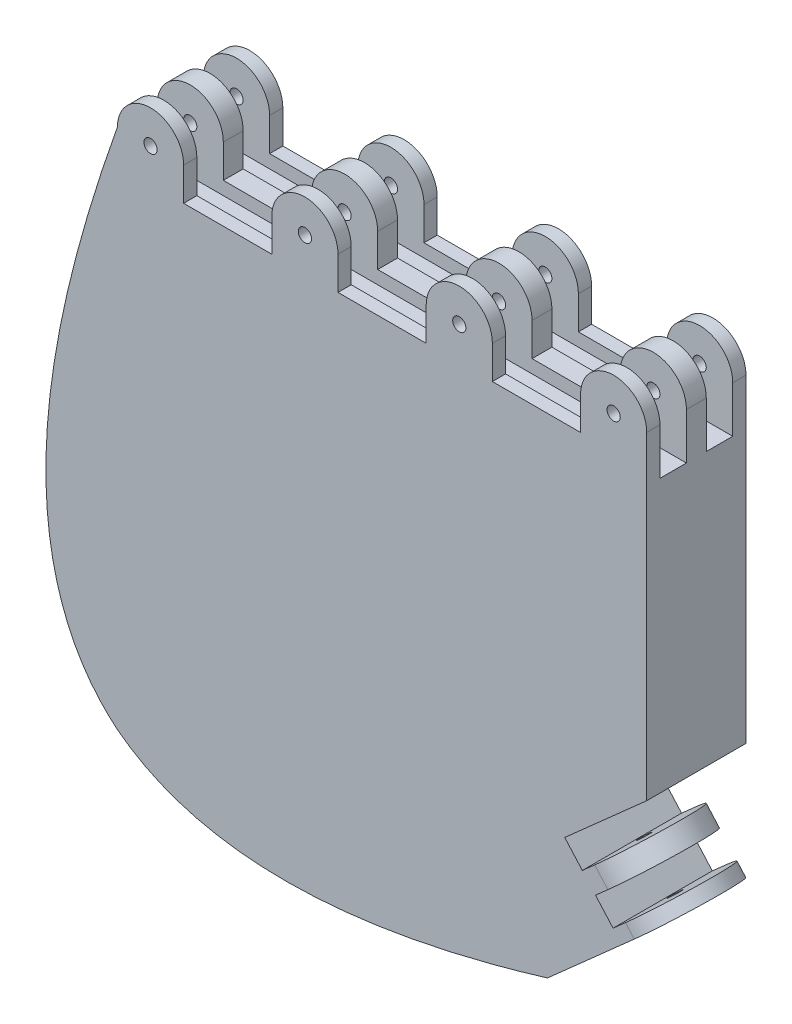
SolidWorks part; units mm, degrees
ref_plane "Plan de face" through (0, 0, 0) normal (0, 0, 1) x (1, 0, 0)
ref_plane "Plan de dessus" through (0, 0, 0) normal (0, 1, 0) x (1, 0, 0)
ref_plane "Plan de droite" through (0, 0, 0) normal (1, 0, 0) x (0, 0, -1)
sketch "Esquisse1" plane through (0, 0, 0) normal (0, 0, 1) x (1, 0, 0)
  line L2 (-10, -18.9105) -> (8.7187, -2.288)
  line L3 (8.7187, -2.288) -> (7.3907, -0.7925)
  line L4 (7.3907, -0.7925) -> (-0.0867, -7.4325)
  line L5 (-0.0867, -7.4325) -> (-2.7427, -4.4416)
  line L6 (-70, 60) -> (-70, 0) construction
  line L7 (-2.7427, -4.4416) -> (4.7347, 2.1984)
  line L8 (4.7347, 2.1984) -> (2.7427, 4.4416)
  line L9 (2.7427, 4.4416) -> (-4.7347, -2.1984)
  line L10 (-4.7347, -2.1984) -> (-7.3907, 0.7925)
  line L11 (-7.3907, 0.7925) -> (5, 11.7957)
  line L12 (5, 11.7957) -> (5, 65)
  line L13 (5, 65) -> (-5, 65)
  line L14 (-5, 65) -> (-5, 55)
  line L15 (-5, 55) -> (-18.3333, 55)
  line L16 (-18.3333, 55) -> (-18.3333, 65)
  line L17 (-18.3333, 65) -> (-28.3333, 65)
  line L18 (-28.3333, 65) -> (-28.3333, 55)
  line L19 (-28.3333, 55) -> (-41.6667, 55)
  line L20 (-41.6667, 55) -> (-41.6667, 65)
  line L21 (-41.6667, 65) -> (-51.6667, 65)
  line L22 (-51.6667, 65) -> (-51.6667, 55)
  line L23 (-51.6667, 55) -> (-65, 55)
  line L24 (-65, 55) -> (-65, 65)
  line L25 (-65, 65) -> (-75, 65)
  line L26 (-75, 65) -> (-75, -18.9105) construction
  line L27 (-75, -18.9105) -> (-10, -18.9105) construction
  line L28 (-70, 60) -> (-46.6667, 60) construction
  line L29 (0, 0) -> (37.3866, 33.2) construction
  line L30 (0, 60) -> (0, 0) construction
  line L31 (-23.3333, 60) -> (0, 60) construction
  line L32 (-46.6667, 60) -> (-23.3333, 60) construction
  line L33 (-65, 60) -> (-75, 60)
  line L34 (-41.6667, 60) -> (-51.6667, 60)
  line L35 (-18.3333, 60) -> (-28.3333, 60)
  line L36 (-5, 60) -> (5, 60)
  circle A0 centre (0, 60) radius 1
  circle A1 centre (-23.3333, 60) radius 1
  circle A2 centre (-70, 60) radius 1
  circle A3 centre (-46.6667, 60) radius 1
  arc A4 (-5, 60) -> (5, 60) centre (0, 60) cw
  arc A5 (-28.3333, 60) -> (-18.3333, 60) centre (-23.3333, 60) cw
  arc A6 (-51.6667, 60) -> (-41.6667, 60) centre (-46.6667, 60) cw
  arc A7 (-75, 60) -> (-65, 60) centre (-70, 60) cw
  spline S0 degree 2 poles (-75, 65) (-116.9553, -51.4105) (-10, -18.9105) knots 0 0 0 1 1 1
  spline S1 degree 2 poles (-75, 60) (-114.4553, -51.4105) (-10, -18.9105) knots 0 0 0 1 1 1
  point P31 (3.7387, 3.32)
  dimension "D26" = 2
  dimension "D27" = 2
  dimension "D30" = 2
  dimension "D31" = 2
  dimension "D1" = 5
  dimension "D2" = 4
  dimension "D3" = 0
  dimension "D4" = 2
  dimension "D5" = 3
  dimension "D6" = 4
  dimension "D7" = 5
  dimension "D8" = 5
  dimension "D9" = 5
  dimension "D10" = 10
  dimension "D11" = 5
  dimension "D12" = 5
  dimension "D13" = 5
  dimension "D14" = 5
  dimension "D15" = 5
  dimension "D16" = 5
  dimension "D17" = 5
  dimension "D18" = 5
  dimension "D19" = 5
  dimension "D20" = 5
  dimension "D21" = 5
  dimension "D22" = 5
  dimension "D23" = 5
  dimension "D24" = 5
  dimension "D25" = 65
  dimension "D28" = 10
  dimension "D29" = 10
extrude "Boss.-Extru.1" add sketch "Esquisse1" along normal blind 12.5 and the other way blind 2.5 contours L33 S1 S0 L2 L3 L4 L5 L7 L8 L9 L10 L11 L12 L36 A0 L14 L15 L16 L35 A1 L18 L19 L20 L34 A3 L22 L23 L24 A2 | A7 L33 A2 | A6 L34 A3 | A5 L35 A1 | A4 L36 A0 region at (-40.161, 17.9034, 0) region at (-70, 62.1928, 0) region at (-46.6667, 62.1928, 0) region at (0, 62.1928, 0) region at (-23.3333, 62.1928, 0)
sketch "Esquisse2" plane through (5, 0, 0) normal (1, 0, 0) x (0, 0, -1)
  line L0 (-12.5, 60) -> (2.5, 60)
  line L1 (2.5, 60) -> (2.5, 53)
  line L2 (2.5, 11.7957) -> (2.5, 60) construction
  line L3 (2.5, 53) -> (-12.5, 53)
  line L4 (-12.5, 11.7957) -> (-12.5, 60) construction
  line L5 (-12.5, 53) -> (-12.5, 65)
  line L6 (-12.5, 65) -> (2.5, 65)
  line L7 (2.5, 65) -> (2.5, 53)
  line L9 (-10.5, 65) -> (-6.5, 65)
  line L11 (-6.5, 65) -> (-3.5, 65)
  line L13 (-3.5, 65) -> (0.5, 65)
  line L15 (-10.5, 65) -> (-10.5, 53)
  line L16 (-10.5, 53) -> (-6.5, 53)
  line L17 (-6.5, 53) -> (-6.5, 65)
  line L18 (-3.5, 65) -> (-3.5, 53)
  line L19 (-3.5, 53) -> (0.5, 53)
  line L20 (0.5, 53) -> (0.5, 65)
  line L21 (-10.5, 53) -> (-6.5, 53)
  line L22 (-3.5, 53) -> (0.5, 53)
  line L23 (-10.5, 65) -> (-10.5, 53)
  line L24 (-10.5, 65) -> (-6.5, 65)
  line L25 (-10.5, 53) -> (-6.5, 53)
  line L26 (-6.5, 65) -> (-6.5, 53)
  line L27 (-3.5, 65) -> (-3.5, 53)
  line L28 (-3.5, 65) -> (0.5, 65)
  line L29 (-3.5, 53) -> (0.5, 53)
  line L30 (0.5, 65) -> (0.5, 53)
  dimension "D1" = 12
  dimension "D2" = 7
  dimension "D3" = 3
  dimension "D4" = 4
  dimension "D5" = 2
  dimension "D6" = 4
  dimension "D7" = 12
  dimension "D8" = 12
extrude "Enlèv. mat.-Extru.1" cut sketch "Esquisse2" against normal through all contours L0 L6 | L9 L0 | L0 L6 | L13 L0 | L23 L24 L26 L25 | L27 L28 L30 L29 region at (5, 62.5, 8.5) region at (5, 56.5, 8.5) region at (5, 62.5, 1.5) region at (5, 56.5, 1.5)
sketch "Esquisse3" plane through (4.98, -5.608, 0) normal (0.664, -0.7477, 0) x (0.7477, 0.664, 0)
  line L0 (-2.5, 12.5) -> (-2.5, -2.5)
  line L1 (-20.0339, 12.5) -> (5, 12.5) construction
  line L2 (-20.0339, -2.5) -> (5, -2.5) construction
  line L3 (5, -2.5) -> (5, 12.5) construction
  line L4 (-2.5, 12.5) -> (5, 12.5)
  line L5 (5, 12.5) -> (5, -2.5)
  line L6 (5, -2.5) -> (-2.5, -2.5)
  arc A0 (-2.5, 12.5) -> (-2.5, -2.5) centre (-2.5, 5) cw
  circle A1 centre (-2.5, 5) radius 1
  line M3 (5, -2.5) -> (5, 12.5)
  line M4 (5, 12.5) -> (-20.0339, 12.5)
  line M6 (-20.0339, -2.5) -> (5, -2.5)
  dimension "D2" = 2
  dimension "D1" = 7.5
extrude "Enlèv. mat.-Extru.2" cut sketch "Esquisse3" against normal blind 12.5 contours A0 L5 M4 | A0 M3 M6 | A1 region at (7.466, -3.4004, 10.8247) region at (7.466, -3.4004, -0.8247)
